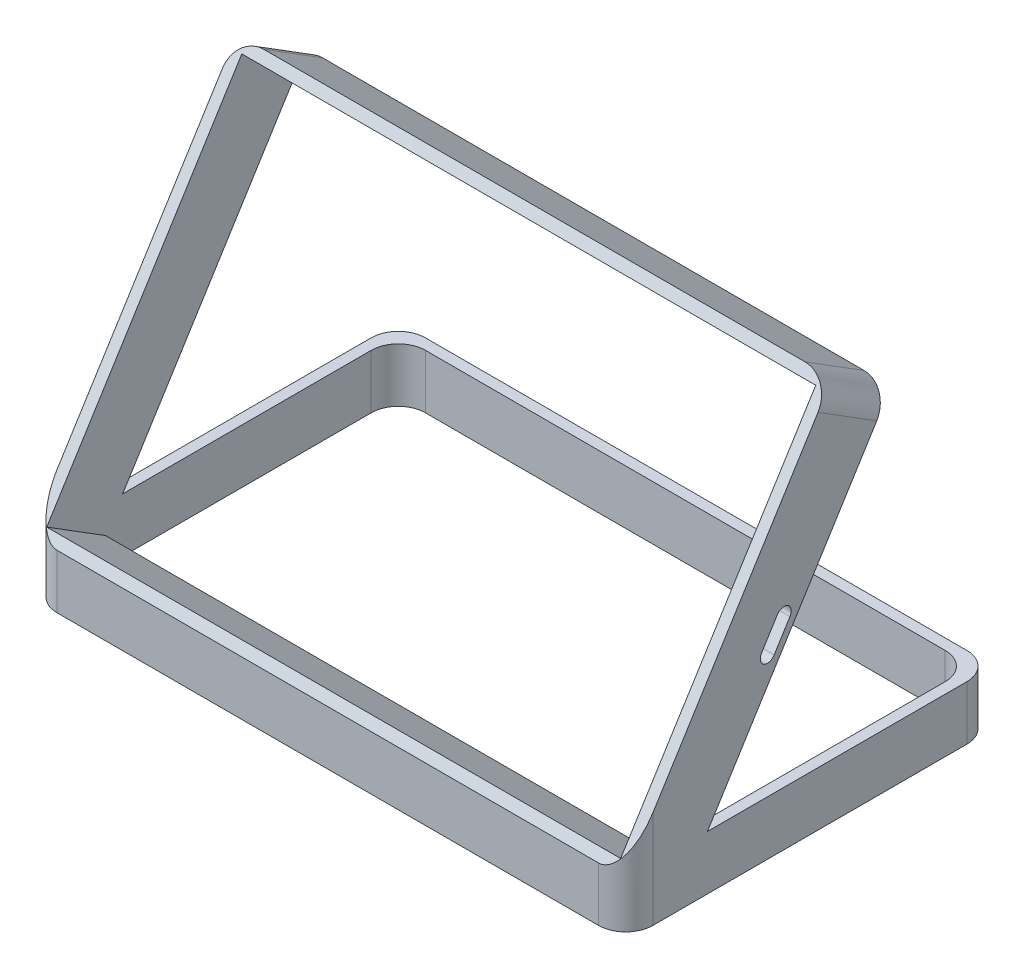
SolidWorks part; units mm, degrees
ref_plane "Front Plane" through (0, 0, 0) normal (0, 0, 1) x (1, 0, 0)
ref_plane "Top Plane" through (0, 0, 0) normal (0, 1, 0) x (1, 0, 0)
ref_plane "Right Plane" through (0, 0, 0) normal (1, 0, 0) x (0, 0, -1)
sketch "Sketch1" plane through (0, 0, 0) normal (0, 1, 0) x (1, 0, 0)
  line L1 (-55, 34) -> (55, 34)
  line L2 (-55, 34) -> (-55, -34)
  line L3 (-55, -34) -> (55, -34)
  line L4 (55, 34) -> (55, -34)
  line L5 (53, -32) -> (-53, -32)
  line L6 (53, -32) -> (53, 32)
  line L7 (53, 32) -> (-53, 32)
  line L8 (-53, -32) -> (-53, 32)
  line L9 (53, -32) -> (-53, 32) construction
  line L10 (53, 32) -> (-53, -32) construction
  point P4 (0, 0)
  dimension "D1" = 110
  dimension "D2" = 55
  dimension "D3" = 68
  dimension "D4" = 34
  dimension "D5" = 2
  dimension "D6" = 2
extrude "Boss-Extrude1" add sketch "Sketch1" along normal blind 10
ref_plane "Plane1" through (0, 18.0876, 28.9463) normal (0, 0.5299, 0.848) x (1, 0, 0)
ref_plane "Plane11" through (0, 2, 0) normal (0, -1, 0) x (-1, 0, 0)
sketch "Sketch16" plane through (0, 2, 0) normal (0, -1, 0) x (1, 0, 0)
  line L11 (-55, 34) -> (55, 34) construction
  line L12 (-47.5, 34) -> (-39.5, 34)
  line L13 (-47.5, 34) -> (-47.5, 24)
  line L14 (-47.5, 24) -> (-39.5, 24)
  line L15 (-39.5, 34) -> (-39.5, 24)
  line L17 (-55, -34) -> (-55, 34) construction
  line L18 (0, -5.5) -> (0, 5.5) construction
  line L19 (39.5, 34) -> (39.5, 24)
  line L20 (47.5, 24) -> (39.5, 24)
  line L21 (47.5, 34) -> (47.5, 24)
  line L22 (47.5, 34) -> (39.5, 34)
  circle A2 centre (-43.5, 28) radius 1.5
  circle A3 centre (43.5, 28) radius 1.5
  dimension "D3" = 3
  dimension "D1" = 8
  dimension "D2" = 10
  dimension "D4" = 6
  dimension "D5" = 4
  dimension "D6" = 7.5
extrude "Boss-Extrude11" add sketch "Sketch16" against normal up to surface (8 mm away) up to face at (0, 10, 0)
sketch "Sketch2" plane through (0, 18.0876, 28.9463) normal (0, 0.5299, 0.848) x (1, 0, 0)
  line L1 (-55, -9.5368) -> (55, -9.5368)
  line L2 (-55, -9.5368) -> (-55, 62.4632)
  line L3 (-55, 62.4632) -> (55, 62.4632)
  line L4 (55, -9.5368) -> (55, 62.4632)
  dimension "D1" = 110
  dimension "D2" = 72
extrude "Boss-Extrude2" add sketch "Sketch2" against normal blind 12.8
sketch "Sketch9" plane through (55, 0, 0) normal (1, 0, 0) x (0, 0, -1)
  line L0 (-5.2079, 39.4706) -> (-9.7122, 32.2622)
  line L1 (-9.7122, 32.2622) -> (-7.3801, 30.805)
  line L2 (-7.3801, 30.805) -> (-2.8758, 38.0134)
  line L3 (-2.8758, 38.0134) -> (-5.2079, 39.4706)
  line L4 (-9.1273, 49.8046) -> (-48.7653, -13.6294) construction
  line L5 (-14.9229, 40.5297) -> (-4.0679, 33.7468) construction
  line L6 (-34, 10) -> (4.1542, 71.0595) construction
  line L7 (-18.9065, 10) -> (15.0092, 64.2765) construction
  dimension "D1" = 8.8
  dimension "D2" = 8.5
  dimension "D3" = 2.75
  dimension "D4" = 4.25
extrude "Cut-Extrude3" cut sketch "Sketch9" against normal up to surface (2 mm away) up to face at (53, 5.3279, 7.0086)
sketch "Sketch19" plane through (0, 18.0876, 28.9463) normal (0, 0.5299, 0.848) x (1, 0, 0)
  line L0 (55, -9.5368) -> (55, 62.4632) construction
  line L1 (-53, 60.4632) -> (53, 60.4632)
  line L2 (-53, 60.4632) -> (-53, -7.5368)
  line L3 (-53, -7.5368) -> (53, -7.5368)
  line L4 (53, 60.4632) -> (53, -7.5368)
  line L5 (55, 62.4632) -> (-55, 62.4632) construction
  line L6 (-55, 62.4632) -> (-55, -9.5368) construction
  line L7 (-55, -9.5368) -> (55, -9.5368) construction
  dimension "D1" = 2
  dimension "D2" = 2
  dimension "D3" = 2
  dimension "D4" = 2
extrude "Cut-Extrude4" cut sketch "Sketch19" against normal up to surface (12.8 mm away) up to face at (0, 21.8734, 11.4872)
fillet "Fillet1" radius 5 10 edges at (55, 5, -34) (-55, 5, -34) (-55, 67.668, -9.5817) (55, 67.668, -9.5817) (-55, 5, 34) (55, 5, 34) (53, 5, -32) (-53, 5, -32) (53, 4.3751, 32) (-53, 4.3751, 32)
fillet "Fillet2" radius 1.5 4 edges at (54, 38.0134, 2.8758) (54, 30.805, 7.3801) (54, 32.2622, 9.7122) (54, 39.4706, 5.2079)
fillet "Fillet3" radius 2 8 edges at (-39.5, 5.3751, 32) (-47.5, 5.3751, 32) (-47.5, 2.8757, 24) (-39.5, 2.8757, 24) (39.5, 5.3751, 32) (39.5, 2.8757, 24) (47.5, 2.8757, 24) (47.5, 5.3751, 32)
